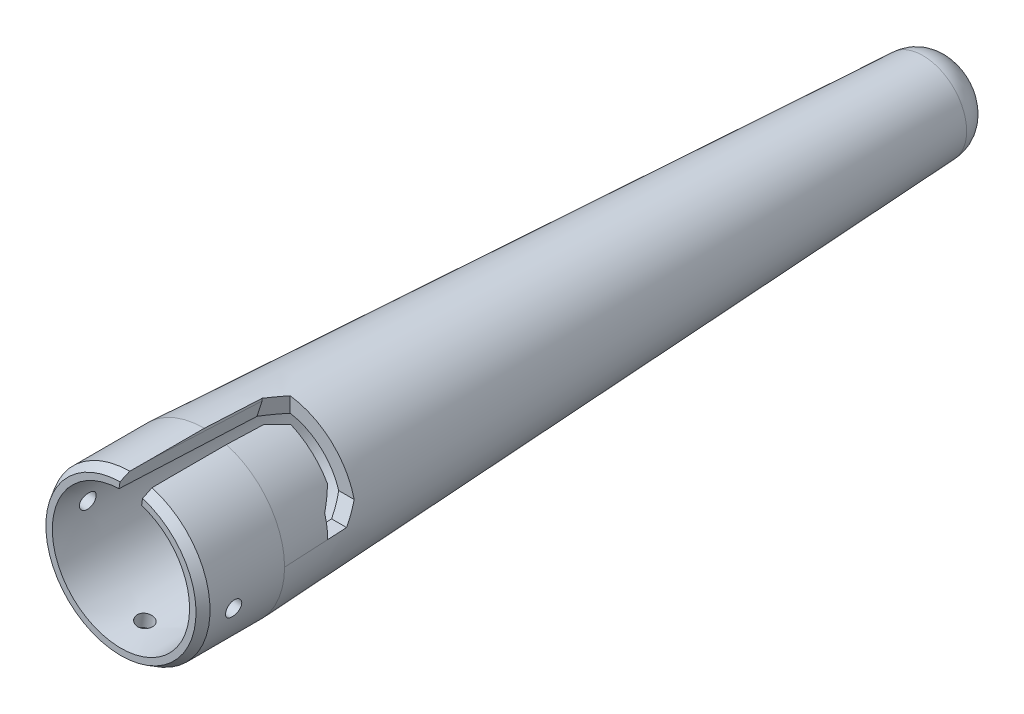
SolidWorks part; units mm, degrees
ref_plane "前视基准面" through (0, 0, 0) normal (0, 0, 1) x (1, 0, 0)
ref_plane "上视基准面" through (0, 0, 0) normal (0, 1, 0) x (1, 0, 0)
ref_plane "右视基准面" through (0, 0, 0) normal (1, 0, 0) x (0, 0, -1)
sketch "草图1" plane through (0, 0, 0) normal (0, 1, 0) x (1, 0, 0)
  line L0 (0, 0) -> (0, 136.6105) construction
  line L5 (-12.5, 0) -> (-6.7981, 125) construction
  line L6 (-12.5, 0) -> (-10.6981, 0)
  line L7 (-10.6981, 0) -> (-5, 124.918)
  line L8 (-2, 129.5843) -> (-2, 127.7843)
  line L9 (-6.7981, 125) -> (-12.5, 13)
  line L10 (-12.5, 13) -> (-12.5, 0)
  arc A2 (-5, 124.918) -> (-2, 127.7843) centre (-2, 124.7811) cw
  arc A3 (-6.7981, 125) -> (-2, 129.5843) centre (-2, 124.7811) cw
  dimension "D1" = 4
  dimension "D2" = 1.8
  dimension "D3" = 12.5
  dimension "D4" = 125
  dimension "D5" = 10
  dimension "D6" = 7.8062
  dimension "D7" = 13
  dimension "D8" = 0.5924
revolve "旋转1" add sketch "草图1" angle 360 about L0
sketch "草图2" plane through (0, 0, 0) normal (0, 1, 0) x (1, 0, 0)
  line L0 (0, 127.7843) -> (0, 112.5619) construction
  line L1 (2, 127.7843) -> (-2, 127.7843) construction
  line L2 (-2, 128.2843) -> (-2, 126.2843)
  line L3 (-2, 126.2843) -> (-3.2, 126.2843)
  line L4 (-3.2, 126.2843) -> (-3.2, 114.2843)
  line L5 (-3.2, 114.2843) -> (-6.1677, 109.7144)
  line L6 (-6.1677, 109.7144) -> (-5.3617, 125.0942)
  line L8 (5, 124.918) -> (-5, 124.918) construction
  arc A0 (-2, 128.2843) -> (-5.3617, 125.0942) centre (-2, 124.918) ccw
  dimension "D1" = 3
  dimension "D2" = 4
  dimension "D3" = 0.5
  dimension "D4" = 1.2
  dimension "D5" = 30
  dimension "D6" = 12
  dimension "D7" = 2
revolve "旋转2" add sketch "草图2" angle 360 about L0
sketch "草图3" plane through (0, 0, 0) normal (0, 1, 0) x (1, 0, 0)
  line L0 (6, 21.6843) -> (15, 21.6843)
  line L1 (15, 21.6843) -> (15, 24.7843)
  line L2 (15, 24.7843) -> (6, 24.7843)
  line L3 (6, 24.7843) -> (6, 21.6843)
  line L4 (2, 129.5843) -> (-2, 129.5843) construction
  dimension "D1" = 3.1
  dimension "D2" = 6
  dimension "D3" = 15
  dimension "D4" = 104.8
ref_plane "基准面1" through (0, 0, -21.6843) normal (0, 0, 1) x (1, 0, 0)
sketch "草图4" plane through (0, 0, -21.6843) normal (0, 0, 1) x (1, 0, 0)
  line L0 (0, 12.5) -> (0, 0) construction
  line L1 (0, 0) -> (10.8253, -6.25) construction
  arc A1 (10.8253, -6.25) -> (0, 12.5) centre (0, 0) ccw
  circle A3 centre (0, 0) radius 12.5 construction
  dimension "D1" = 120
sweep "切除-扫描1" cut profiles "草图3" path "草图4"
sketch "草图5" plane through (0, 0, -21.6843) normal (0, 0, -1) x (-1, 0, 0)
  line L0 (0, 0) -> (0, 14.758)
  line L1 (0, 14.758) -> (-4.0642, 14.1874)
  line L2 (-4.0642, 14.1874) -> (0, 0)
  line L3 (0, 9.709) -> (-2.6738, 9.3336) construction
  arc A0 (0, 9.709) -> (-9.709, 0) centre (0, 0) ccw construction
  dimension "D1" = 2.7
  dimension "D2" = 5
extrude "切除-拉伸1" cut sketch "草图5" against normal through all
sketch "草图6" plane through (0, 0, -21.6843) normal (0, 0, 1) x (1, 0, 0)
  line L0 (0, 0) -> (14.758, 0)
  line L1 (0, 0) -> (14.1874, 4.0642)
  line L2 (14.1874, 4.0642) -> (14.758, 0)
  line L3 (9.709, 0) -> (9.3336, 2.6738) construction
  arc A0 (9.709, 0) -> (2.6738, 9.3336) centre (0, 0) ccw construction
  dimension "D1" = 5
  dimension "D2" = 2.7
extrude "切除-拉伸2" cut sketch "草图6" along normal blind 1.6
ref_plane "基准面2" through (0, 0, -28.7843) normal (0, 0, 1) x (1, 0, 0)
sketch "草图7" plane through (0, 0, 0) normal (0, 0, 1) x (1, 0, 0)
  line L0 (3.4424, 12.0167) -> (0, 12.5)
sketch "草图9" plane through (0, 0, 0) normal (1, 0, 0) x (0, 0, -1)
  line L0 (0, 0) -> (57.3452, 0)
ref_plane "基准面3" through (0, 0, 0) normal (-0.9903, 0.139, 0) x (0, 0, 1)
sketch "草图10" plane through (0, 0, 0) normal (-0.9903, 0.139, 0) x (0, 0, 1)
  line L0 (0, 0) -> (-57.3452, 0) construction
  line L1 (0, -12.5) -> (0, 12.3786) construction
  circle A0 centre (-5.19, 0) radius 1.25
  dimension "D1" = 5.19
  dimension "D2" = 2.5
extrude "切除-拉伸3" cut sketch "草图10" against normal through all both and the other way through all
ref_plane "基准面4" through (0, 0, 0) normal (0.139, 0.9903, 0) x (0, 0, -1)
sketch "草图12" plane through (0, 0, 0) normal (0.139, 0.9903, 0) x (0, 0, -1)
  line L0 (0, 0) -> (57.3452, 0) construction
  line L1 (0, 12.5) -> (0, -12.5) construction
  circle A0 centre (5.19, 0) radius 1.25
  dimension "D1" = 5.19
  dimension "D2" = 2.5
extrude "切除-拉伸4" cut sketch "草图12" against normal through all
chamfer "倒角2" distance 1.6 angle 60 4 edges at (0, 10.7338, -24.7843) (2.9972, 10.4626, -21.6843) (10.7338, 0, -24.7843) (10.4626, 2.9972, -21.6843)
chamfer "倒角3" distance 2 angle 10 2 edges at (2.8274, 9.8698, -9.4565) (0, 10.1961, -11.0065)
chamfer "倒角4" distance 0.8 angle 60 1 edges
chamfer "倒角5" distance 0.6 angle 25 2 edges at (-3.2, 0, -126.2843) (-2, 0, -126.2843)
